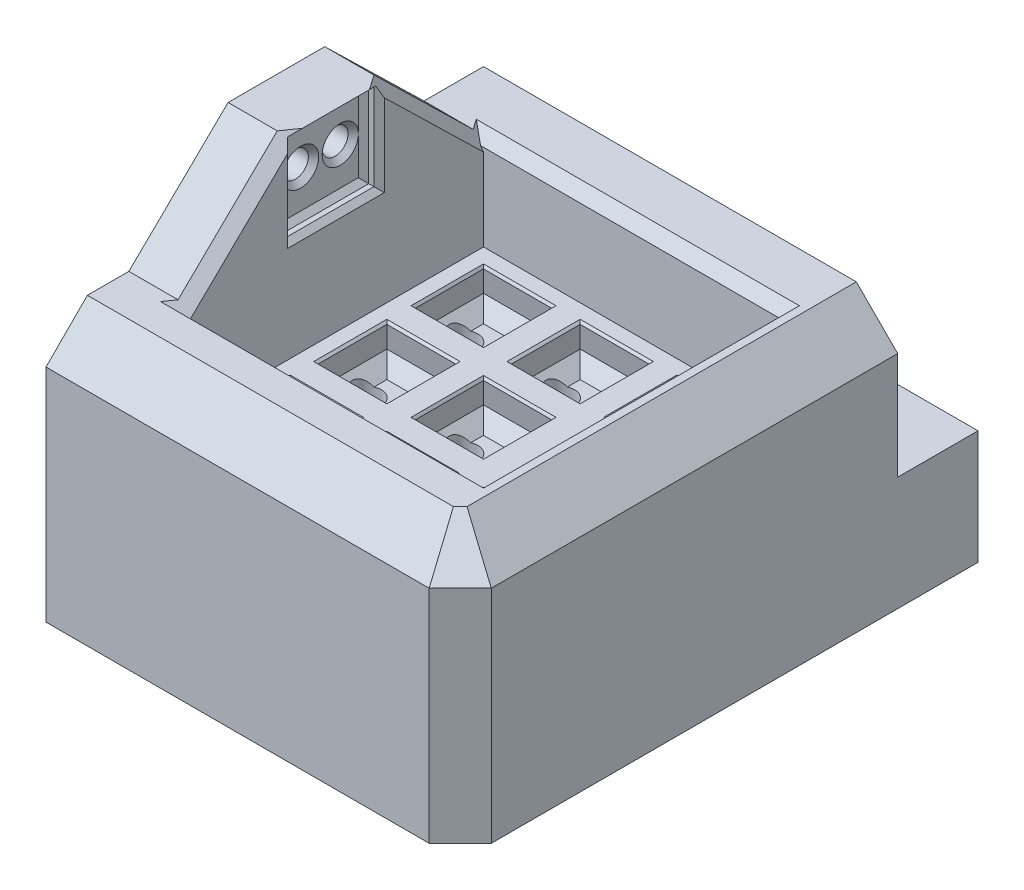
SolidWorks part; units mm, degrees
ref_plane "Front Plane" through (0, 0, 0) normal (0, 0, 1) x (1, 0, 0)
ref_plane "Top Plane" through (0, 0, 0) normal (0, 1, 0) x (1, 0, 0)
ref_plane "Right Plane" through (0, 0, 0) normal (1, 0, 0) x (0, 0, -1)
sketch "Sketch1" plane through (0, 0, 0) normal (0, 1, 0) x (1, 0, 0)
  line L1 (-40, -50) -> (40, -50)
  line L2 (-40, -50) -> (-40, 50)
  line L3 (-40, 50) -> (40, 50)
  line L4 (40, -50) -> (40, 50)
  line L5 (-40, -50) -> (40, 50) construction
  line L6 (-40, 50) -> (40, -50) construction
  point P0 (0, 0)
  dimension "D1" = 100
  dimension "D2" = 80
extrude "Boss-Extrude1" add sketch "Sketch1" against normal blind 22
sketch "Sketch2" plane through (0, -22, 0) normal (0, -1, 0) x (1, 0, 0)
  line L1 (-35.5, -45.5) -> (35.5, -45.5)
  line L2 (-35.5, -45.5) -> (-35.5, 45.5)
  line L3 (-35.5, 45.5) -> (35.5, 45.5)
  line L4 (35.5, -45.5) -> (35.5, 45.5)
  line L5 (-35.5, -45.5) -> (35.5, 45.5) construction
  line L6 (-35.5, 45.5) -> (35.5, -45.5) construction
  point P0 (0, 0)
  dimension "D1" = 71
  dimension "D2" = 91
extrude "Cut-Extrude1" cut sketch "Sketch2" against normal offset from surface (18 mm away) 4 up to face at (0, 0, 0)
sketch "Sketch3" plane through (0, -4, 0) normal (0, -1, 0) x (1, 0, 0)
  line L0 (-35.5, 45.5) -> (35.5, 45.5) construction
  line L1 (-35, -45) -> (35, -45) construction
  line L2 (-35, -45) -> (-35, 45) construction
  line L3 (-35, 45) -> (35, 45) construction
  line L4 (35, -45) -> (35, 45) construction
  line L5 (-35, -45) -> (35, 45) construction
  line L6 (-35, 45) -> (35, -45) construction
  line L7 (-35.5, 45.5) -> (-35.5, -45.5) construction
  line L8 (-35.5, 36.5) -> (-35.5, 45.5)
  line L9 (-35.5, 45.5) -> (-26.5, 45.5)
  circle A0 centre (-32.5, 41.7857) radius 1.55
  arc A1 (-26.5, 45.5) -> (-35.5, 36.5) centre (-35.5, 45.5) cw
  point P0 (0, 0)
  dimension "D4" = 3.1
  dimension "D5" = 9
  dimension "D1" = 70
  dimension "D2" = 90
  dimension "D3" = 2.5
extrude "Boss-Extrude2" add sketch "Sketch3" along normal blind 8
mirror "Mirror1" about plane through (0, 0, 0) normal (0, 0, 1) of "Boss-Extrude2" second plane through (0, 0, 0) second plane normal (1, 0, 0)
sketch "Cube Reference" plane through (0, 0, 0) normal (0, -1, 0) x (1, 0, 0)
  line L0 (-26.5, 45.5) -> (26.5, 45.5) construction
  line L1 (-28, -22.5) -> (28, -22.5)
  line L2 (-28, -22.5) -> (-28, 33.5)
  line L3 (-28, 33.5) -> (28, 33.5)
  line L4 (28, -22.5) -> (28, 33.5)
  line L6 (-9.3333, 33.5) -> (9.3333, 33.5)
  line L7 (-9.3333, 33.5) -> (-9.3333, -22.5)
  line L8 (-9.3333, -22.5) -> (9.3333, -22.5)
  line L9 (9.3333, 33.5) -> (9.3333, -22.5)
  line L10 (-28, 14.8333) -> (28, 14.8333)
  line L11 (-28, 14.8333) -> (-28, -3.8333)
  line L12 (-28, -3.8333) -> (28, -3.8333)
  line L13 (28, 14.8333) -> (28, -3.8333)
  point P0 (0, 33.5)
  dimension "D1" = 56
  dimension "D2" = 56
  dimension "D3" = 12
  dimension "D4" = 9.3333
  dimension "D5" = 9.3333
  dimension "D6" = 18.6667
  dimension "D7" = 18.6667
chamfer "Chamfer6" distance 1 angle 45 8 edges at (-26.5, -8, 45.5) (-35.5, -8, 36.5) (26.5, -8, 45.5) (35.5, -8, 36.5) (-26.5, -8, -45.5) (-35.5, -8, -36.5) (26.5, -8, -45.5) (35.5, -8, -36.5)
ref_plane "Plane2" through (-28, 0, 0) normal (-1, 0, 0) x (0, 0, 1)
sketch "Sketch13" plane through (0, 0, 0) normal (0, 1, 0) x (1, 0, 0)
  line L0 (40, -50) -> (40, 50) construction
  line L1 (40, -50) -> (-40, -50)
  line L2 (40, -50) -> (40, 34.5)
  line L3 (40, 34.5) -> (-40, 34.5)
  line L4 (-40, -50) -> (-40, 34.5)
  line L5 (-40, 50) -> (-40, -50) construction
  line L6 (28, 22.5) -> (28, -33.5) construction
  line L7 (28.5, -34) -> (-28.5, -34)
  line L8 (28.5, -34) -> (28.5, 23)
  line L9 (28.5, 23) -> (-28.5, 23)
  line L10 (-28.5, -34) -> (-28.5, 23)
  line L11 (-28, 22.5) -> (-28, -33.5) construction
  line L12 (-28, 22.5) -> (28, 22.5) construction
  line L13 (-28, -33.5) -> (28, -33.5) construction
  line L14 (-40, -50) -> (40, -50) construction
  dimension "D1" = 0.5
  dimension "D2" = 0.5
  dimension "D3" = 0.5
  dimension "D4" = 0.5
  dimension "D5" = 11.5
extrude "Boss-Extrude4" add sketch "Sketch13" along normal blind 28.6667
sketch "Sketch14" plane through (0, 0, 0) normal (0, 1, 0) x (1, 0, 0)
  line L0 (-27, 21.5) -> (-27, 4.8333)
  line L1 (-27, 4.8333) -> (-10.3333, 4.8333)
  line L2 (-10.3333, 21.5) -> (-10.3333, 4.8333)
  line L3 (-27, 21.5) -> (-10.3333, 21.5)
  line L4 (-8.3333, 21.5) -> (-8.3333, 4.8333)
  line L5 (-28, 3.8333) -> (28, 3.8333) construction
  line L6 (-9.3333, -33.5) -> (-9.3333, 22.5) construction
  line L7 (-8.3333, 4.8333) -> (8.3333, 4.8333)
  line L8 (28.5, 23) -> (-28.5, 23)
  line L9 (28.5, -34) -> (28.5, 23)
  line L10 (-28.5, -34) -> (28.5, -34)
  line L11 (-28.5, 23) -> (-28.5, -34)
  line L12 (28.5, 23) -> (-28.5, 23)
  line L13 (28.5, -34) -> (28.5, 23)
  line L14 (-28.5, -34) -> (28.5, -34)
  line L15 (-28.5, 23) -> (-28.5, -34)
  line L16 (8.3333, 21.5) -> (8.3333, 4.8333)
  line L17 (-8.3333, 21.5) -> (8.3333, 21.5)
  line L18 (27, 21.5) -> (27, 4.8333)
  line L19 (9.3333, -33.5) -> (9.3333, 22.5) construction
  line L20 (-28, 22.5) -> (-9.3333, 22.5) construction
  line L21 (-28, 22.5) -> (-28, 3.8333) construction
  line L22 (-28, 3.8333) -> (-9.3333, 3.8333) construction
  line L23 (-9.3333, 22.5) -> (-9.3333, 3.8333) construction
  line L24 (-28, -14.8333) -> (-9.3333, -14.8333) construction
  line L25 (-28, -14.8333) -> (-28, 3.8333) construction
  line L26 (-28, 3.8333) -> (-9.3333, 3.8333) construction
  line L27 (-9.3333, -14.8333) -> (-9.3333, 3.8333) construction
  line L28 (-9.3333, 22.5) -> (9.3333, 22.5) construction
  line L29 (-9.3333, 22.5) -> (-9.3333, 3.8333) construction
  line L30 (-9.3333, 3.8333) -> (9.3333, 3.8333) construction
  line L31 (9.3333, 22.5) -> (9.3333, 3.8333) construction
  line L32 (-28, -14.8333) -> (28, -14.8333) construction
  line L33 (28, 22.5) -> (9.3333, 22.5) construction
  line L34 (28, 22.5) -> (28, 3.8333) construction
  line L35 (28, 3.8333) -> (9.3333, 3.8333) construction
  line L36 (9.3333, 22.5) -> (9.3333, 3.8333) construction
  line L37 (9.3333, -14.8333) -> (28, -14.8333) construction
  line L38 (9.3333, -14.8333) -> (9.3333, 3.8333) construction
  line L39 (9.3333, 3.8333) -> (28, 3.8333) construction
  line L40 (28, -14.8333) -> (28, 3.8333) construction
  line L41 (27, 4.8333) -> (10.3333, 4.8333)
  line L42 (9.3333, -14.8333) -> (-9.3333, -14.8333) construction
  line L43 (9.3333, -14.8333) -> (9.3333, 3.8333) construction
  line L44 (9.3333, 3.8333) -> (-9.3333, 3.8333) construction
  line L45 (-9.3333, -14.8333) -> (-9.3333, 3.8333) construction
  line L46 (-28, -33.5) -> (-9.3333, -33.5) construction
  line L47 (-28, -33.5) -> (-28, -14.8333) construction
  line L48 (-28, -14.8333) -> (-9.3333, -14.8333) construction
  line L49 (-9.3333, -33.5) -> (-9.3333, -14.8333) construction
  line L50 (-9.3333, -14.8333) -> (9.3333, -14.8333) construction
  line L51 (-9.3333, -14.8333) -> (-9.3333, -33.5) construction
  line L52 (-9.3333, -33.5) -> (9.3333, -33.5) construction
  line L53 (9.3333, -14.8333) -> (9.3333, -33.5) construction
  line L54 (10.3333, 21.5) -> (10.3333, 4.8333)
  line L55 (27, 21.5) -> (10.3333, 21.5)
  line L56 (-27, -13.8333) -> (-27, 2.8333)
  line L57 (-27, 2.8333) -> (-10.3333, 2.8333)
  line L58 (-10.3333, -13.8333) -> (-10.3333, 2.8333)
  line L59 (-27, -13.8333) -> (-10.3333, -13.8333)
  line L60 (8.3333, -13.8333) -> (8.3333, 2.8333)
  line L61 (8.3333, 2.8333) -> (-8.3333, 2.8333)
  line L62 (-8.3333, -13.8333) -> (-8.3333, 2.8333)
  line L63 (8.3333, -13.8333) -> (-8.3333, -13.8333)
  line L64 (10.3333, -13.8333) -> (10.3333, 2.8333)
  line L65 (10.3333, 2.8333) -> (27, 2.8333)
  line L66 (27, -13.8333) -> (27, 2.8333)
  line L67 (10.3333, -13.8333) -> (27, -13.8333)
  line L68 (-27, -32.5) -> (-27, -15.8333)
  line L69 (-27, -15.8333) -> (-10.3333, -15.8333)
  line L70 (-10.3333, -32.5) -> (-10.3333, -15.8333)
  line L71 (-27, -32.5) -> (-10.3333, -32.5)
  line L72 (-8.3333, -15.8333) -> (-8.3333, -32.5)
  line L73 (-8.3333, -32.5) -> (8.3333, -32.5)
  line L74 (8.3333, -15.8333) -> (8.3333, -32.5)
  line L75 (-8.3333, -15.8333) -> (8.3333, -15.8333)
  line L77 (9.3333, -14.8333) -> (28, -14.8333) construction
  line L78 (9.3333, -14.8333) -> (9.3333, -33.5) construction
  line L79 (9.3333, -33.5) -> (28, -33.5) construction
  line L80 (28, -14.8333) -> (28, -33.5) construction
  line L81 (10.3333, -15.8333) -> (10.3333, -32.5)
  line L82 (10.3333, -32.5) -> (27, -32.5)
  line L83 (27, -15.8333) -> (27, -32.5)
  line L84 (10.3333, -15.8333) -> (27, -15.8333)
  line M94 (-28.5, 23) -> (-28.5, -34)
  line M95 (-28.5, -34) -> (28.5, -34)
  line M96 (28.5, -34) -> (28.5, 23)
  line M97 (28.5, 23) -> (-28.5, 23)
  dimension "D1" = 0.5
  dimension "D2" = 1
  dimension "D3" = 1
  dimension "D4" = 1
  dimension "D5" = 1
  dimension "D6" = 1
  dimension "D7" = 1
  dimension "D8" = 1
  dimension "D9" = 1
  dimension "D10" = 1
extrude "Boss-Extrude5" add sketch "Sketch14" along normal blind 10 draft 10 contours L72 L75 L74 L73 L71 L68 L69 L70 L67 L64 L65 L66 L4 L17 L16 L7 L0 L3 L2 L1 L55 L18 L41 L54 L59 L56 L57 L58 L60 L63 L62 L61 L81 L84 L83 L82 M97 M94 M95 M96 draft outward yes
sketch "Sketch15" plane through (0, 0, 0) normal (0, 1, 0) x (1, 0, 0)
  line L0 (27, -15.8333) -> (10.3333, -15.8333) construction
  line L1 (10.3333, -15.8333) -> (10.3333, -32.5) construction
  line L2 (10.3333, -32.5) -> (27, -32.5) construction
  line L3 (27, -32.5) -> (27, -15.8333) construction
  line L4 (8.3333, -15.8333) -> (-8.3333, -15.8333) construction
  line L5 (-8.3333, -15.8333) -> (-8.3333, -32.5) construction
  line L6 (-8.3333, -32.5) -> (8.3333, -32.5) construction
  line L7 (8.3333, -32.5) -> (8.3333, -15.8333) construction
  line L8 (-27, -15.8333) -> (-27, -32.5) construction
  line L9 (-27, -32.5) -> (-10.3333, -32.5) construction
  line L10 (-10.3333, -32.5) -> (-10.3333, -15.8333) construction
  line L11 (-10.3333, -15.8333) -> (-27, -15.8333) construction
  line L12 (-27, 2.8333) -> (-27, -13.8333) construction
  line L13 (-27, -13.8333) -> (-10.3333, -13.8333) construction
  line L14 (-10.3333, -13.8333) -> (-10.3333, 2.8333) construction
  line L15 (-10.3333, 2.8333) -> (-27, 2.8333) construction
  line L16 (-8.3333, -13.8333) -> (8.3333, -13.8333) construction
  line L17 (8.3333, -13.8333) -> (8.3333, 2.8333) construction
  line L18 (8.3333, 2.8333) -> (-8.3333, 2.8333) construction
  line L19 (-8.3333, 2.8333) -> (-8.3333, -13.8333) construction
  line L20 (10.3333, 2.8333) -> (10.3333, -13.8333) construction
  line L21 (10.3333, -13.8333) -> (27, -13.8333) construction
  line L22 (27, -13.8333) -> (27, 2.8333) construction
  line L23 (27, 2.8333) -> (10.3333, 2.8333) construction
  line L24 (27, 4.8333) -> (27, 21.5) construction
  line L25 (27, 21.5) -> (10.3333, 21.5) construction
  line L26 (10.3333, 21.5) -> (10.3333, 4.8333) construction
  line L27 (10.3333, 4.8333) -> (27, 4.8333) construction
  line L28 (8.3333, 21.5) -> (-8.3333, 21.5) construction
  line L29 (-8.3333, 21.5) -> (-8.3333, 4.8333) construction
  line L30 (-8.3333, 4.8333) -> (8.3333, 4.8333) construction
  line L31 (8.3333, 4.8333) -> (8.3333, 21.5) construction
  line L32 (-10.3333, 21.5) -> (-27, 21.5) construction
  line L33 (-27, 21.5) -> (-27, 4.8333) construction
  line L34 (-27, 4.8333) -> (-10.3333, 4.8333) construction
  line L35 (-10.3333, 4.8333) -> (-10.3333, 21.5) construction
  line L36 (27, -15.8333) -> (10.3333, -15.8333)
  line L37 (10.3333, -15.8333) -> (10.3333, -32.5)
  line L38 (10.3333, -32.5) -> (27, -32.5)
  line L39 (27, -32.5) -> (27, -15.8333)
  line L40 (8.3333, -15.8333) -> (-8.3333, -15.8333)
  line L41 (-8.3333, -15.8333) -> (-8.3333, -32.5)
  line L42 (-8.3333, -32.5) -> (8.3333, -32.5)
  line L43 (8.3333, -32.5) -> (8.3333, -15.8333)
  line L44 (-27, -15.8333) -> (-27, -32.5)
  line L45 (-27, -32.5) -> (-10.3333, -32.5)
  line L46 (-10.3333, -32.5) -> (-10.3333, -15.8333)
  line L47 (-10.3333, -15.8333) -> (-27, -15.8333)
  line L48 (-27, 2.8333) -> (-27, -13.8333)
  line L49 (-27, -13.8333) -> (-10.3333, -13.8333)
  line L50 (-10.3333, -13.8333) -> (-10.3333, 2.8333)
  line L51 (-10.3333, 2.8333) -> (-27, 2.8333)
  line L52 (-8.3333, -13.8333) -> (8.3333, -13.8333)
  line L53 (8.3333, -13.8333) -> (8.3333, 2.8333)
  line L54 (8.3333, 2.8333) -> (-8.3333, 2.8333)
  line L55 (-8.3333, 2.8333) -> (-8.3333, -13.8333)
  line L56 (10.3333, 2.8333) -> (10.3333, -13.8333)
  line L57 (10.3333, -13.8333) -> (27, -13.8333)
  line L58 (27, -13.8333) -> (27, 2.8333)
  line L59 (27, 2.8333) -> (10.3333, 2.8333)
  line L60 (27, 4.8333) -> (27, 21.5)
  line L61 (27, 21.5) -> (10.3333, 21.5)
  line L62 (10.3333, 21.5) -> (10.3333, 4.8333)
  line L63 (10.3333, 4.8333) -> (27, 4.8333)
  line L64 (8.3333, 21.5) -> (-8.3333, 21.5)
  line L65 (-8.3333, 21.5) -> (-8.3333, 4.8333)
  line L66 (-8.3333, 4.8333) -> (8.3333, 4.8333)
  line L67 (8.3333, 4.8333) -> (8.3333, 21.5)
  line L68 (-10.3333, 21.5) -> (-27, 21.5)
  line L69 (-27, 21.5) -> (-27, 4.8333)
  line L70 (-27, 4.8333) -> (-10.3333, 4.8333)
  line L71 (-10.3333, 4.8333) -> (-10.3333, 21.5)
extrude "Boss-Extrude6" add sketch "Sketch15" along normal blind 2
chamfer "Chamfer11" distance 0.5 angle 45 35 edges at (25.2367, 10, -13.1667) (18.6667, 10, -19.7367) (12.0966, 10, -13.1667) (18.6667, 10, -6.5966) (18.6667, 10, -1.0701) (25.2367, 10, 5.5) (18.6667, 10, 12.0701) (18.6667, 10, 30.7367) (25.2367, 10, 24.1667) (18.6667, 10, 17.5966) (12.0966, 10, 24.1667) (0, 10, 12.0701) (6.5701, 10, 5.5) (0, 10, -1.0701) (-6.5701, 10, 5.5) (0, 10, 30.7367) (6.5701, 10, 24.1667) (0, 10, 17.5966) (-6.5701, 10, 24.1667) (-18.6667, 10, 30.7367) (-12.0966, 10, 24.1667) (-25.2367, 10, 24.1667) (-18.6667, 10, 17.5966) (-18.6667, 10, 12.0701) (-25.2367, 10, 5.5) (-18.6667, 10, -1.0701) (-12.0966, 10, 5.5) (0, 10, -6.5966) (6.5701, 10, -13.1667) (0, 10, -19.7367) (-6.5701, 10, -13.1667) (-18.6667, 10, -6.5966) (-12.0966, 10, -13.1667) (-25.2367, 10, -13.1667) (-18.6667, 10, -19.7367)
chamfer "Chamfer12" distance 3 angle 45 36 edges at (18.6667, 2, 32.1473) (10.686, 2, 24.1667) (18.6667, 2, 16.186) (26.6473, 2, 24.1667) (0, 2, 32.1473) (-7.9807, 2, 24.1667) (0, 2, 16.186) (7.9807, 2, 24.1667) (-10.686, 2, 24.1667) (-18.6667, 2, 32.1473) (-26.6473, 2, 24.1667) (-18.6667, 2, 16.186) (-10.686, 2, 5.5) (-18.6667, 2, 13.4807) (-26.6473, 2, 5.5) (-18.6667, 2, -2.4807) (0, 2, -2.4807) (7.9807, 2, 5.5) (0, 2, 13.4807) (-7.9807, 2, 5.5) (26.6473, 2, 5.5) (18.6667, 2, 13.4807) (10.686, 2, 5.5) (18.6667, 2, -2.4807) (10.686, 2, -13.1667) (18.6667, 2, -21.1473) (26.6473, 2, -13.1667) (18.6667, 2, -5.186) (0, 2, -5.186) (-7.9807, 2, -13.1667) (0, 2, -21.1473) (7.9807, 2, -13.1667) (-18.6667, 2, -5.186) (-26.6473, 2, -13.1667) (-18.6667, 2, -21.1473) (-10.686, 2, -13.1667)
sketch "Sketch5" plane through (0, -4, 0) normal (0, -1, 0) x (1, 0, 0)
  line L0 (-28, -22.5) -> (-28, 33.5) construction
  line L1 (-9.3333, 33.5) -> (-9.3333, -22.5) construction
  line L2 (-28, 14.8333) -> (28, 14.8333) construction
  circle A0 centre (-22.5, 24.1667) radius 2.75
  circle A1 centre (-14.8333, 24.1667) radius 2.75
  dimension "D4" = 5.5
  dimension "D5" = 5.5
  dimension "D1" = 5.5
  dimension "D2" = 5.5
  dimension "D3" = 9.3333
extrude "Cut-Extrude2" cut sketch "Sketch5" against normal through all
pattern_linear "LPattern1" count 3 spacing 18.6667 along (1, 0, 0) count 3 spacing 18.6667 along (0, 0, -1) of "Cut-Extrude2"
chamfer "Chamfer13" distance 1 angle 45 34 edges at (-22.5, -4, 21.4167) (-14.8333, -4, 21.4167) (3.8333, -4, 21.4167) (-3.8333, -4, 2.75) (3.8333, -4, 2.75) (-3.8333, -4, -15.9167) (-14.8333, -4, 2.75) (-22.5, -4, -15.9167) (-14.8333, -4, -15.9167) (-3.8333, -4, 21.4167) (22.5, -4, 2.75) (14.8333, -4, -15.9167) (22.5, -4, -15.9167) (3.8333, -4, -15.9167) (14.8333, -4, 21.4167) (22.5, -4, 21.4167) (14.8333, -4, 2.75) (-22.5, -4, 2.75) (29.136, -4, 39.136) (0, -4, -45.5) (29.136, -4, -39.136) (35.5, -4, 0) (0, -4, 45.5) (-29.136, -4, 39.136) (-35.5, -4, 0) (-29.136, -4, -39.136) (26.0315, -4, -44.9685) (34.9685, -4, -36.0315) (-34.9685, -4, -36.0315) (-26.0315, -4, -44.9685) (-26.0315, -4, 44.9685) (-34.9685, -4, 36.0315) (34.9685, -4, 36.0315) (26.0315, -4, 44.9685)
sketch "Sketch17" plane through (0, -4, 0) normal (0, -1, 0) x (1, 0, 0)
  line L0 (40, -34.5) -> (-40, -34.5) construction
  line L5 (-25.5, -45.5) -> (25.5, -45.5)
  line L6 (-25.5, -45.5) -> (-25.5, -36.5)
  line L7 (-25.5, -36.5) -> (25.5, -36.5)
  line L8 (25.5, -45.5) -> (25.5, -36.5)
  point P5 (0, -36.5)
  dimension "D1" = 2
extrude "Cut-Extrude3" cut sketch "Sketch17" against normal blind 12
sketch "Sketch18" plane through (-28.5, 0, 0) normal (1, 0, 0) x (0, 0, -1)
  line L0 (23, 28.6667) -> (23, 10) construction
  line L1 (-34, 10) -> (23, 10)
  line L2 (-34, 10) -> (-34, 28.6667)
  line L3 (-34, 28.6667) -> (23, 28.6667) construction
  line L4 (23, 10) -> (23, 28.6667)
  line L5 (-34, 28.6667) -> (-14.8333, 47.3333)
  line L6 (-14.8333, 47.3333) -> (3.8333, 47.3333)
  line L7 (3.8333, 47.3333) -> (23, 28.6667)
  point P11 (-5.5, 28.6667)
  point P12 (-5.5, 47.3333)
  line M8 (-34, 28.6667) -> (-34, 10)
  line M9 (-34, 10) -> (23, 10)
  line M10 (23, 10) -> (23, 28.6667)
  line M11 (23, 28.6667) -> (-34, 28.6667)
  dimension "D1" = 18.6667
  dimension "D2" = 18.6667
  dimension "D3" = 18.6667
extrude "Boss-Extrude7" add sketch "Sketch18" against normal up to surface (11.5 mm away) contours L5 L3 L7 L6 | L3 L2 L4 M11 | M11 M8 M9 M10 up to face at (-40, 2.2222, -11.5)
sketch "Sketch20" plane through (-28.5, 0, 0) normal (1, 0, 0) x (0, 0, -1)
  line L0 (-13.8333, 46.3333) -> (-13.8333, 29.6667)
  line L1 (-14.8333, 47.3333) -> (3.8333, 47.3333) construction
  line L2 (-14.8333, 47.3333) -> (-14.8333, 28.6667) construction
  line L3 (-14.8333, 28.6667) -> (3.8333, 28.6667) construction
  line L4 (3.8333, 47.3333) -> (3.8333, 28.6667) construction
  line L5 (-13.8333, 29.6667) -> (2.8333, 29.6667)
  line L6 (2.8333, 46.3333) -> (2.8333, 29.6667)
  line L7 (-13.8333, 46.3333) -> (2.8333, 46.3333)
  dimension "D1" = 18.6667
  dimension "D2" = 18.6667
  dimension "D3" = 1
extrude "Cut-Extrude5" cut sketch "Sketch20" against normal blind 3
sketch "Sketch19" plane through (-28.5, 0, 0) normal (1, 0, 0) x (0, 0, -1)
  line L0 (-14.8333, 47.3333) -> (3.8333, 47.3333) construction
  line L1 (-14.8333, 47.3333) -> (3.8333, 47.3333) construction
  line L2 (-14.8333, 47.3333) -> (-14.8333, 28.6667) construction
  line L3 (-14.8333, 28.6667) -> (3.8333, 28.6667) construction
  line L4 (3.8333, 47.3333) -> (3.8333, 28.6667) construction
  line L5 (-34, 10) -> (23, 10) construction
  circle A0 centre (-9.3333, 38) radius 2.5
  circle A1 centre (-1.6667, 38) radius 2.5
  point P6 (-5.5, 47.3333)
  point P7 (-5.5, 47.3333)
  point P14 (-14.8333, 38)
  dimension "D4" = 5
  dimension "D5" = 5
  dimension "D1" = 18.6667
  dimension "D2" = 18.6667
  dimension "D3" = 18.6667
  dimension "D6" = 5.5
  dimension "D7" = 5.5
extrude "Cut-Extrude4" cut sketch "Sketch19" against normal through all
chamfer "Chamfer20" distance 1 angle 45 6 edges at (-31.5, 38, -2.8333) (-31.5, 29.6667, 5.5) (-31.5, 38, 13.8333) (-31.5, 46.3333, 5.5) (-31.5, 38, 4.1667) (-31.5, 38, 11.8333)
chamfer "Chamfer21" distance 1 angle 45 4 edges at (-28.5, 29.6667, 5.5) (-28.5, 38, 13.8333) (-28.5, 46.3333, 5.5) (-28.5, 38, -2.8333)
chamfer "Chamfer23" distance 2 angle 45 2 edges at (-28.5, 38, 24.4167) (-28.5, 38, -13.4167)
chamfer "Chamfer22" distance 2 angle 45 3 edges at (-1, 28.6667, 34) (28.5, 28.6667, 5.5) (-1, 28.6667, -23)
chamfer "Chamfer24" distance 6 angle 45 1 edges at (40, 3.3333, 50)
chamfer "Chamfer25" distance 8 angle 45 3 edges at (40, 28.6667, 4.75) (37, 28.6667, 47) (-3, 28.6667, 50)
chamfer "Chamfer26" distance 2 angle 45 1 edges at (-40, -11, -50)
chamfer "Chamfer28" distance 1 angle 45 4 edges at (35.5, -22, 0) (0, -22, -45.5) (-35.5, -22, 0) (0, -22, 45.5)
chamfer "Chamfer29" distance 0.5 angle 45 4 edges at (25.5, 0, -41) (0, 0, -36.5) (0, 0, -45.5) (-25.5, 0, -41)
chamfer "Chamfer30" distance 2 angle 45 3 edges at (-25.5, -4, -40.2929) (0, -4, -36.5) (25.5, -4, -40.2929)
